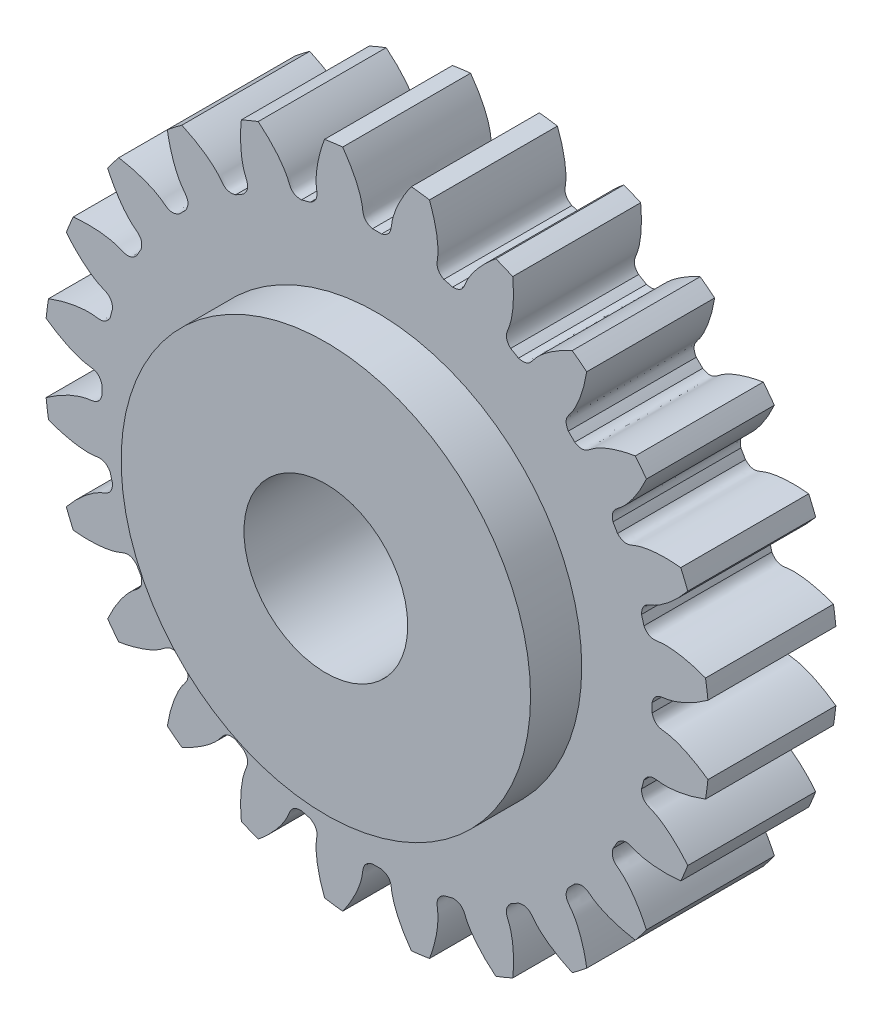
SolidWorks part; units mm, degrees
ref_plane "前视基准面" through (0, 0, 0) normal (0, 0, 1) x (1, 0, 0)
ref_plane "上视基准面" through (0, 0, 0) normal (0, 1, 0) x (1, 0, 0)
ref_plane "右视基准面" through (0, 0, 0) normal (1, 0, 0) x (0, 0, -1)
other "Configuration Table"
sketch "草图1" plane through (0, 0, 0) normal (0, 0, 1) x (1, 0, 0)
  circle A0 centre (0, 0) radius 6.5
extrude "凸台-拉伸1" add sketch "草图1" along normal blind 2.5
ref_axis "基准轴1" through (0, 0, 2.5) along (0, 0, -1)
sketch "草图2" plane through (0, 0, 0) normal (0, 0, 1) x (1, 0, 0)
  line L0 (0, 0) -> (0, 6.5) construction
  circle A0 centre (0, 0) radius 6.5 construction
  arc A1 (0.0884, 5.3743) -> (-0.0884, 5.3743) centre (0, 0) ccw
  arc A2 (1.5578, 7.3471) -> (-1.5578, 7.3471) centre (0, 0) ccw
  spline S0 degree 3 poles (0.0884, 5.3743) (0.284, 5.4284) (0.2695, 5.5579) (0.2931, 5.6863) (0.2965, 5.7029) (0.3007, 5.7216) (0.3058, 5.7424) (0.312, 5.7653) (0.3191, 5.7902) (0.3275, 5.8171) (0.3371, 5.846) (0.348, 5.8769) (0.3604, 5.9096) (0.3742, 5.9441) (0.3896, 5.9805) (0.4067, 6.0185) (0.4254, 6.0583) (0.446, 6.0997) (0.4684, 6.1427) (0.4928, 6.1872) (0.5192, 6.2332) (0.5476, 6.2806) (0.5782, 6.3293) (0.611, 6.3792) (0.6461, 6.4304) (0.6834, 6.4827) (0.7232, 6.536) (0.7654, 6.5903) (0.8101, 6.6456) (0.8574, 6.7016) (0.9073, 6.7583) (0.9598, 6.8158) (1.015, 6.8738) (1.0729, 6.9322) (1.1336, 6.9911) (1.1972, 7.0503) (1.2635, 7.1097) (1.3328, 7.1693) (1.4302, 7.2497) (1.506, 7.3084) (1.5578, 7.3471) knots 0 0 0 0 0.143961 0.149818 0.156577 0.164236 0.172796 0.182258 0.19262 0.203884 0.216049 0.229115 0.243082 0.25795 0.273719 0.290389 0.30796 0.326433 0.345806 0.366081 0.387257 0.409333 0.432311 0.45619 0.48097 0.506651 0.533234 0.560717 0.589101 0.618387 0.648574 0.679661 0.71165 0.74454 0.778331 0.813023 0.848616 0.885111 0.922506 1 1 1 1
  spline S1 degree 3 poles (-0.0884, 5.3743) (-0.284, 5.4284) (-0.2695, 5.5579) (-0.2931, 5.6863) (-0.2965, 5.7029) (-0.3007, 5.7216) (-0.3058, 5.7424) (-0.312, 5.7653) (-0.3191, 5.7902) (-0.3275, 5.8171) (-0.3371, 5.846) (-0.348, 5.8769) (-0.3604, 5.9096) (-0.3742, 5.9441) (-0.3896, 5.9805) (-0.4067, 6.0185) (-0.4254, 6.0583) (-0.446, 6.0997) (-0.4684, 6.1427) (-0.4928, 6.1872) (-0.5192, 6.2332) (-0.5476, 6.2806) (-0.5782, 6.3293) (-0.611, 6.3792) (-0.6461, 6.4304) (-0.6834, 6.4827) (-0.7232, 6.536) (-0.7654, 6.5903) (-0.8101, 6.6456) (-0.8574, 6.7016) (-0.9073, 6.7583) (-0.9598, 6.8158) (-1.015, 6.8738) (-1.0729, 6.9322) (-1.1336, 6.9911) (-1.1972, 7.0503) (-1.2635, 7.1097) (-1.3328, 7.1693) (-1.4302, 7.2497) (-1.506, 7.3084) (-1.5578, 7.3471) knots 0 0 0 0 0.143961 0.149818 0.156577 0.164236 0.172796 0.182258 0.19262 0.203884 0.216049 0.229115 0.243082 0.25795 0.273719 0.290389 0.30796 0.326433 0.345806 0.366081 0.387257 0.409333 0.432311 0.45619 0.48097 0.506651 0.533234 0.560717 0.589101 0.618387 0.648574 0.679661 0.71165 0.74454 0.778331 0.813023 0.848616 0.885111 0.922506 1 1 1 1
extrude "切除-拉伸1" cut sketch "草图2" along normal through all
pattern_circular "阵列(圆周)1" count 24 every 15 about axis through (0, 0, 2.5) along (0, 0, -1) of "切除-拉伸1"
sketch "草图3" plane through (0, 0, 0) normal (0, 0, 1) x (1, 0, 0)
  circle A0 centre (0, 0) radius 6 construction
  dimension "Dn" = 12
sketch "草图5" plane through (0, 0, 2.5) normal (0, 0, 1) x (1, 0, 0)
  circle A0 centre (0, 0) radius 4
  dimension "D1" = 8
extrude "凸台-拉伸2" add sketch "草图5" along normal blind 1
sketch "草图4" plane through (0, 0, 2.5) normal (0, 0, 1) x (1, 0, 0)
  circle A0 centre (0, 0) radius 1.6
  dimension "D1" = 3.2
extrude "切除-拉伸2" cut sketch "草图4" against normal mid plane 10
